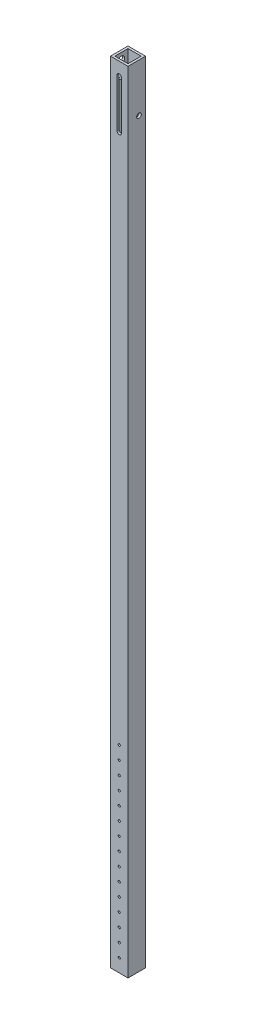
SolidWorks part; units mm, degrees
material "6061-T6 (SS)"
ref_plane "Front Plane" through (0, 0, 0) normal (0, 0, 1) x (1, 0, 0)
ref_plane "Top Plane" through (0, 0, 0) normal (0, 1, 0) x (1, 0, 0)
ref_plane "Right Plane" through (0, 0, 0) normal (1, 0, 0) x (0, 0, -1)
sketch "Sketch1" plane through (0, 0, 0) normal (0, 1, 0) x (1, 0, 0)
  line L0 (9.525, 9.525) -> (-9.525, 9.525)
  line L1 (12.7, -12.7) -> (-12.7, -12.7)
  line L2 (12.7, -12.7) -> (12.7, 12.7)
  line L3 (12.7, 12.7) -> (-12.7, 12.7)
  line L4 (-12.7, -12.7) -> (-12.7, 12.7)
  line L5 (12.7, -12.7) -> (-12.7, 12.7) construction
  line L6 (12.7, 12.7) -> (-12.7, -12.7) construction
  line L7 (-9.525, -9.525) -> (-9.525, 9.525)
  line L8 (9.525, -9.525) -> (-9.525, -9.525)
  line L9 (9.525, -9.525) -> (9.525, 9.525)
  point P0 (0, 0)
  dimension "D1" = 25.4
  dimension "D2" = 3.175
extrude "Boss-Extrude1" add sketch "Sketch1" along normal blind 1143
sketch "Sketch2" plane through (0, 0, -12.7) normal (0, 0, -1) x (-1, 0, 0)
  line L0 (0, 990.6) -> (0, 1104.9) construction
  line L1 (-3.175, 990.6) -> (-3.175, 1104.9)
  line L2 (3.175, 990.6) -> (3.175, 1104.9)
  line L3 (-12.7, 1143) -> (12.7, 1143) construction
  arc A0 (-3.175, 990.6) -> (3.175, 990.6) centre (0, 990.6) ccw
  arc A1 (3.175, 1104.9) -> (-3.175, 1104.9) centre (0, 1104.9) ccw
  point P3 (0, 1047.75)
  dimension "D2" = 38.1
  dimension "D1" = 6.35
  dimension "D3" = 114.3
extrude "Cut-Extrude1" cut sketch "Sketch2" against normal up to next
sketch "Sketch3" plane through (0, 0, 12.7) normal (0, 0, 1) x (1, 0, 0)
  line L0 (0, 1123.95) -> (0, 1054.1) construction
  line L1 (3.175, 1123.95) -> (3.175, 1054.1)
  line L2 (-3.175, 1123.95) -> (-3.175, 1054.1)
  line L3 (-12.7, 1143) -> (12.7, 1143) construction
  arc A0 (3.175, 1123.95) -> (-3.175, 1123.95) centre (0, 1123.95) ccw
  arc A1 (-3.175, 1054.1) -> (3.175, 1054.1) centre (0, 1054.1) ccw
  point P3 (0, 1089.025)
  dimension "D2" = 19.05
  dimension "D1" = 6.35
  dimension "D3" = 69.85
extrude "Cut-Extrude2" cut sketch "Sketch3" against normal up to next
sketch "Sketch4" plane through (-12.7, 0, 0) normal (-1, 0, 0) x (0, 0, 1)
  line L0 (-12.7, 1143) -> (12.7, 1143) construction
  line L2 (-12.7, 1143) -> (-12.7, 0) construction
  circle A0 centre (-3.175, 1073.15) radius 3.3782
  point P4 (73.3381, 1073.15)
  point P5 (0, 1073.15)
  dimension "D1" = 6.7564
  dimension "D2" = 69.85
  dimension "D3" = 9.525
extrude "Cut-Extrude3" cut sketch "Sketch4" against normal through all
sketch "Sketch5" plane through (-12.7, 0, 0) normal (-1, 0, 0) x (0, 0, 1)
  line L0 (-12.7, 1143) -> (-12.7, 0) construction
  line L1 (-12.7, 1143) -> (12.7, 1143) construction
  line L2 (-12.7, 1143) -> (-12.7, 1104.9) construction
  circle A0 centre (0, 1133.475) radius 4.7625
  circle A1 centre (0, 1114.425) radius 4.7625
  dimension "D1" = 9.525
  dimension "D2" = 12.7
  dimension "D3" = 9.525
  dimension "D4" = 38.1
  dimension "D5" = 9.525
extrude "Cut-Extrude4" cut sketch "Sketch5" against normal up to next
sketch "Sketch6" plane through (0, 0, 12.7) normal (0, 0, 1) x (1, 0, 0)
  line L0 (-12.7, 0) -> (-12.7, 304.8) construction
  line L1 (-12.7, 1143) -> (-12.7, 0) construction
  line L2 (-12.7, 0) -> (12.7, 0) construction
  line L3 (12.7, 1143) -> (12.7, 0) construction
  circle A28 centre (0, 19.05) radius 1.5875
  circle A29 centre (0, 38.1) radius 1.5875
  circle A30 centre (0, 57.15) radius 1.5875
  circle A31 centre (0, 76.2) radius 1.5875
  circle A32 centre (0, 95.25) radius 1.5875
  circle A33 centre (0, 114.3) radius 1.5875
  circle A34 centre (0, 133.35) radius 1.5875
  circle A35 centre (0, 152.4) radius 1.5875
  circle A36 centre (0, 171.45) radius 1.5875
  circle A37 centre (0, 190.5) radius 1.5875
  circle A38 centre (0, 209.55) radius 1.5875
  circle A39 centre (0, 228.6) radius 1.5875
  circle A40 centre (0, 247.65) radius 1.5875
  circle A41 centre (0, 266.7) radius 1.5875
  circle A42 centre (0, 285.75) radius 1.5875
  dimension "D3" = 19.05
  dimension "D5" = 15
  dimension "D6" = 19.05
  dimension "D2" = 3.175
  dimension "D4" = 12.7
  dimension "D1" = 304.8
extrude "Cut-Extrude5" cut sketch "Sketch6" against normal through all
